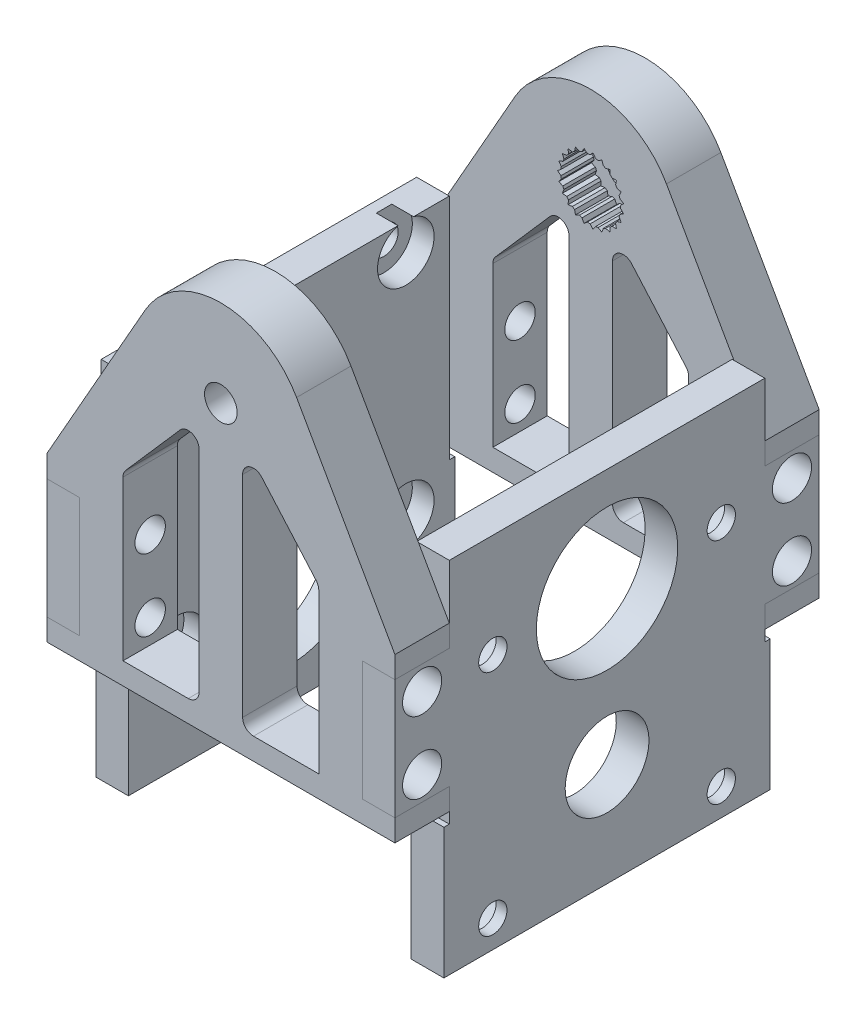
SolidWorks part; units mm, degrees
ref_plane "正面" through (0, 0, 0) normal (0, 0, 1) x (1, 0, 0)
ref_plane "平面" through (0, 0, 0) normal (0, 1, 0) x (1, 0, 0)
ref_plane "右側面" through (0, 0, 0) normal (1, 0, 0) x (0, 0, -1)
sketch "ｽｹｯﾁ1" plane through (0, 0, 0) normal (0, 0, 1) x (1, 0, 0)
  line L0 (-16, -12) -> (-16, -27)
  line L1 (-16, -27) -> (16, -27)
  line L2 (16, -27) -> (16, -12)
  line L3 (16, -12) -> (6.9593, 3.9457)
  line L4 (-6.9593, 3.9457) -> (-16, -12)
  line L5 (0, 0) -> (0, -27) construction
  line L6 (-16, -12) -> (16, -12) construction
  circle A0 centre (0, 0) radius 2.75
  arc A1 (6.9593, 3.9457) -> (-6.9593, 3.9457) centre (0, 0) ccw
  dimension "D1" = 5.5
  dimension "D6" = 8
  dimension "D2" = 16
  dimension "D3" = 16
  dimension "D4" = 12
  dimension "D5" = 15
extrude "ﾎﾞｽ - 押し出し1" add sketch "ｽｹｯﾁ1" along normal blind 3
sketch "ｽｹｯﾁ19" plane through (0, 0, 3) normal (0, 0, 1) x (1, 0, 0)
  line L0 (0, 0) -> (0, 2.75) construction
  line L1 (0, 0) -> (0.3745, 2.7244) construction
  line L2 (0, 0) -> (0.7419, 2.648) construction
  line L3 (0, 0) -> (1.0956, 2.5223) construction
  line L4 (0, 0) -> (1.4289, 2.3497) construction
  line L5 (0, 0) -> (1.7355, 2.1332) construction
  line L6 (0, 0) -> (2.0098, 1.877) construction
  line L7 (0, 0) -> (2.2467, 1.5859) construction
  line L8 (0, 0) -> (2.4417, 1.2652) construction
  line L9 (0, 0) -> (2.5912, 0.9209) construction
  line L10 (0, 0) -> (2.6925, 0.5595) construction
  line L11 (0, 0) -> (2.7436, 0.1877) construction
  line L12 (0, 0) -> (2.7436, -0.1877) construction
  line L13 (0, 0) -> (2.6925, -0.5595) construction
  line L14 (0, 0) -> (2.5912, -0.9209) construction
  line L15 (0, 0) -> (2.4417, -1.2652) construction
  line L16 (0, 0) -> (2.2467, -1.5859) construction
  line L17 (0, 0) -> (2.0098, -1.877) construction
  line L18 (0, 0) -> (1.7355, -2.1332) construction
  line L19 (0, 0) -> (1.4289, -2.3497) construction
  line L20 (0, 0) -> (1.0956, -2.5223) construction
  line L21 (0, 0) -> (0.7419, -2.648) construction
  line L22 (0, 0) -> (0.3745, -2.7244) construction
  line L23 (0, 0) -> (0, -2.75) construction
  line L24 (0, 0) -> (-0.3745, -2.7244) construction
  line L25 (0, 0) -> (-0.7419, -2.648) construction
  line L26 (0, 0) -> (-1.0956, -2.5223) construction
  line L27 (0, 0) -> (-1.4289, -2.3497) construction
  line L28 (0, 0) -> (-1.7355, -2.1332) construction
  line L29 (0, 0) -> (-2.0098, -1.877) construction
  line L30 (0, 0) -> (-2.2467, -1.5859) construction
  line L31 (0, 0) -> (-2.4417, -1.2652) construction
  line L32 (0, 0) -> (-2.5912, -0.9209) construction
  line L33 (0, 0) -> (-2.6925, -0.5595) construction
  line L34 (0, 0) -> (-2.7436, -0.1877) construction
  line L35 (0, 0) -> (-2.7436, 0.1877) construction
  line L36 (0, 0) -> (-2.6925, 0.5595) construction
  line L37 (0, 0) -> (-2.5912, 0.9209) construction
  line L38 (0, 0) -> (-2.4417, 1.2652) construction
  line L39 (0, 0) -> (-2.2467, 1.5859) construction
  line L40 (0, 0) -> (-2.0098, 1.877) construction
  line L41 (0, 0) -> (-1.7355, 2.1332) construction
  line L42 (0, 0) -> (-1.4289, 2.3497) construction
  line L43 (0, 0) -> (-1.0956, 2.5223) construction
  line L44 (0, 0) -> (-0.7419, 2.648) construction
  line L45 (0, 0) -> (-0.3745, 2.7244) construction
  line L46 (0, 0) -> (0.2081, 3.0429) construction
  line L47 (0.2081, 3.0429) -> (-0.0626, 2.7493)
  line L48 (0.2081, 3.0429) -> (0.4364, 2.7152)
  line L49 (-0.0626, 2.7493) -> (0, 0) construction
  line L50 (0, 0) -> (0.4364, 2.7152) construction
  line L51 (1.0214, 2.8739) -> (0.6815, 2.6642)
  line L52 (1.0214, 2.8739) -> (1.1527, 2.4967)
  line L53 (1.7589, 2.4918) -> (1.375, 2.3816)
  line L54 (1.7589, 2.4918) -> (1.7836, 2.0931)
  line L55 (2.3659, 1.9248) -> (1.9666, 1.9223)
  line L56 (2.3659, 1.9248) -> (2.2822, 1.5343)
  line L57 (2.7975, 1.2151) -> (2.4123, 1.3204)
  line L58 (2.7975, 1.2151) -> (2.6115, 0.8617)
  line L59 (3.0216, 0.4153) -> (2.679, 0.6206)
  line L60 (3.0216, 0.4153) -> (2.7472, 0.1252)
  line L61 (3.0216, -0.4153) -> (2.7472, -0.1252)
  line L62 (3.0216, -0.4153) -> (2.679, -0.6206)
  line L63 (2.7975, -1.2151) -> (2.6115, -0.8617)
  line L64 (2.7975, -1.2151) -> (2.4123, -1.3204)
  line L65 (2.3659, -1.9248) -> (2.2822, -1.5343)
  line L66 (2.3659, -1.9248) -> (1.9666, -1.9223)
  line L67 (1.7589, -2.4918) -> (1.7836, -2.0931)
  line L68 (1.7589, -2.4918) -> (1.375, -2.3816)
  line L69 (1.0214, -2.8739) -> (1.1527, -2.4967)
  line L70 (1.0214, -2.8739) -> (0.6815, -2.6642)
  line L71 (0.2081, -3.0429) -> (0.4364, -2.7152)
  line L72 (0.2081, -3.0429) -> (-0.0626, -2.7493)
  line L73 (-0.6205, -2.9862) -> (-0.3123, -2.7322)
  line L74 (-0.6205, -2.9862) -> (-0.802, -2.6304)
  line L75 (-1.4032, -2.708) -> (-1.0379, -2.5466)
  line L76 (-1.4032, -2.708) -> (-1.482, -2.3165)
  line L77 (-2.0818, -2.229) -> (-1.6865, -2.1722)
  line L78 (-2.0818, -2.229) -> (-2.052, -1.8308)
  line L79 (-2.606, -1.5847) -> (-2.21, -1.6366)
  line L80 (-2.606, -1.5847) -> (-2.4699, -1.2093)
  line L81 (-2.9369, -0.8229) -> (-2.5696, -0.9797)
  line L82 (-2.9369, -0.8229) -> (-2.7045, -0.4981)
  line L83 (-3.05, 0) -> (-2.7386, -0.2501)
  line L84 (-3.05, 0) -> (-2.7386, 0.2501)
  line L85 (-2.9369, 0.8229) -> (-2.7045, 0.4981)
  line L86 (-2.9369, 0.8229) -> (-2.5696, 0.9797)
  line L87 (-2.606, 1.5847) -> (-2.4699, 1.2093)
  line L88 (-2.606, 1.5847) -> (-2.21, 1.6366)
  line L89 (-2.0818, 2.229) -> (-2.052, 1.8308)
  line L90 (-2.0818, 2.229) -> (-1.6865, 2.1722)
  line L91 (-1.4032, 2.708) -> (-1.482, 2.3165)
  line L92 (-1.4032, 2.708) -> (-1.0379, 2.5466)
  line L93 (-0.6205, 2.9862) -> (-0.802, 2.6304)
  line L94 (-0.6205, 2.9862) -> (-0.3123, 2.7322)
  circle A0 centre (0, 0) radius 2.75 construction
  arc A1 (0, 2.75) -> (0.3745, 2.7244) centre (0, 0) cw construction
  circle A2 centre (0, 0) radius 3.05 construction
  arc A3 (-0.0626, 2.7493) -> (0.4364, 2.7152) centre (0, 0) cw
  arc A4 (0.6815, 2.6642) -> (1.1527, 2.4967) centre (0, 0) cw
  arc A5 (1.375, 2.3816) -> (1.7836, 2.0931) centre (0, 0) cw
  arc A6 (1.9666, 1.9223) -> (2.2822, 1.5343) centre (0, 0) cw
  arc A7 (2.4123, 1.3204) -> (2.6115, 0.8617) centre (0, 0) cw
  arc A8 (2.679, 0.6206) -> (2.7472, 0.1252) centre (0, 0) cw
  arc A9 (2.7472, -0.1252) -> (2.679, -0.6206) centre (0, 0) cw
  arc A10 (2.6115, -0.8617) -> (2.4123, -1.3204) centre (0, 0) cw
  arc A11 (2.2822, -1.5343) -> (1.9666, -1.9223) centre (0, 0) cw
  arc A12 (1.7836, -2.0931) -> (1.375, -2.3816) centre (0, 0) cw
  arc A13 (1.1527, -2.4967) -> (0.6815, -2.6642) centre (0, 0) cw
  arc A14 (0.4364, -2.7152) -> (-0.0626, -2.7493) centre (0, 0) cw
  arc A15 (-0.3123, -2.7322) -> (-0.802, -2.6304) centre (0, 0) cw
  arc A16 (-1.0379, -2.5466) -> (-1.482, -2.3165) centre (0, 0) cw
  arc A17 (-1.6865, -2.1722) -> (-2.052, -1.8308) centre (0, 0) cw
  arc A18 (-2.21, -1.6366) -> (-2.4699, -1.2093) centre (0, 0) cw
  arc A19 (-2.5696, -0.9797) -> (-2.7045, -0.4981) centre (0, 0) cw
  arc A20 (-2.7386, -0.2501) -> (-2.7386, 0.2501) centre (0, 0) cw
  arc A21 (-2.7045, 0.4981) -> (-2.5696, 0.9797) centre (0, 0) cw
  arc A22 (-2.4699, 1.2093) -> (-2.21, 1.6366) centre (0, 0) cw
  arc A23 (-2.052, 1.8308) -> (-1.6865, 2.1722) centre (0, 0) cw
  arc A24 (-1.482, 2.3165) -> (-1.0379, 2.5466) centre (0, 0) cw
  arc A25 (-0.802, 2.6304) -> (-0.3123, 2.7322) centre (0, 0) cw
  point P7 (0.1877, 2.7436)
  point P52 (0, 0)
  point P60 (0.1877, 2.7436)
  point P126 (0, 0)
  dimension "D2" = 6.1
  dimension "D3" = 10.435
  dimension "D1" = 46
  dimension "D4" = 23
extrude "ｶｯﾄ - 押し出し6" cut sketch "ｽｹｯﾁ19" against normal through all
sketch "ｽｹｯﾁ2" plane through (0, 0, 0) normal (0, 0, -1) x (-1, 0, 0)
  line L5 (16, -12) -> (6.9593, 3.9457)
  line L6 (-6.9593, 3.9457) -> (-16, -12)
  line L7 (-16, -12) -> (-16, -27)
  line L8 (-16, -27) -> (16, -27)
  line L9 (16, -27) -> (16, -12)
  line L10 (16, -12) -> (6.9593, 3.9457)
  line L11 (-6.9593, 3.9457) -> (-16, -12)
  line L12 (-16, -12) -> (-16, -27)
  line L13 (-16, -27) -> (16, -27)
  line L14 (16, -27) -> (16, -12)
  arc A1 (6.9593, 3.9457) -> (-6.9593, 3.9457) centre (0, 0) ccw
  arc A2 (6.9593, 3.9457) -> (-6.9593, 3.9457) centre (0, 0) ccw
  dimension "D1" = 0
extrude "ﾎﾞｽ - 押し出し2" add sketch "ｽｹｯﾁ2" along normal blind 2
ref_plane "平面1" through (0, 0, 33.5) normal (0, 0, 1) x (1, 0, 0)
sketch "ｽｹｯﾁ3" plane through (0, 0, 33.5) normal (0, 0, 1) x (1, 0, 0)
  line L5 (-6.9593, 3.9457) -> (-16, -12)
  line L6 (-16, -12) -> (-16, -27)
  line L7 (-16, -27) -> (16, -27)
  line L8 (16, -27) -> (16, -12)
  line L9 (16, -12) -> (6.9593, 3.9457)
  line L10 (-6.9593, 3.9457) -> (-16, -12)
  line L11 (-16, -12) -> (-16, -27)
  line L12 (-16, -27) -> (16, -27)
  line L13 (16, -27) -> (16, -12)
  line L14 (16, -12) -> (6.9593, 3.9457)
  circle A0 centre (0, 0) radius 2.75 construction
  arc A1 (6.9593, 3.9457) -> (-6.9593, 3.9457) centre (0, 0) ccw
  arc A2 (6.9593, 3.9457) -> (-6.9593, 3.9457) centre (0, 0) ccw
  circle A3 centre (0, 0) radius 2.75 construction
  circle A4 centre (0, 0) radius 3.6
  dimension "D2" = 7.2
  dimension "D1" = 0
extrude "ﾎﾞｽ - 押し出し3" add sketch "ｽｹｯﾁ3" against normal blind 1.5 separate body
sketch "ｽｹｯﾁ4" plane through (0, 0, 33.5) normal (0, 0, 1) x (1, 0, 0)
  line L5 (-6.9593, 3.9457) -> (-16, -12)
  line L6 (-16, -12) -> (-16, -27)
  line L7 (-16, -27) -> (16, -27)
  line L8 (16, -27) -> (16, -12)
  line L9 (16, -12) -> (6.9593, 3.9457)
  line L10 (-6.9593, 3.9457) -> (-16, -12)
  line L11 (-16, -12) -> (-16, -27)
  line L12 (-16, -27) -> (16, -27)
  line L13 (16, -27) -> (16, -12)
  line L14 (16, -12) -> (6.9593, 3.9457)
  arc A1 (6.9593, 3.9457) -> (-6.9593, 3.9457) centre (0, 0) ccw
  arc A2 (6.9593, 3.9457) -> (-6.9593, 3.9457) centre (0, 0) ccw
  dimension "D1" = 0
extrude "ﾎﾞｽ - 押し出し4" add sketch "ｽｹｯﾁ4" along normal blind 3.5
sketch "ｽｹｯﾁ5" plane through (0, 0, -2) normal (0, 0, -1) x (-1, 0, 0)
  line L0 (-16, -12) -> (-16, -27) construction
  line L1 (-16, -14) -> (-13, -14)
  line L2 (-16, -14) -> (-16, -25)
  line L3 (-16, -25) -> (-13, -25)
  line L4 (-13, -14) -> (-13, -25)
  line L5 (-16, -14) -> (-13, -25) construction
  line L6 (-16, -25) -> (-13, -14) construction
  line L7 (16, -27) -> (16, -12) construction
  line L8 (16, -14) -> (13, -14)
  line L9 (16, -14) -> (16, -25)
  line L10 (16, -25) -> (13, -25)
  line L11 (13, -14) -> (13, -25)
  line L12 (16, -14) -> (13, -25) construction
  line L13 (16, -25) -> (13, -14) construction
  line L14 (-16, -27) -> (16, -27) construction
  line L15 (-16, -12) -> (16, -12) construction
  line L16 (-6.9593, 3.9457) -> (-16, -12) construction
  point P4 (-14.5, -19.5)
  point P11 (14.5, -19.5)
  dimension "D1" = 3
  dimension "D2" = 3
  dimension "D3" = 2
  dimension "D4" = 2
extrude "ｶｯﾄ - 押し出し1" cut sketch "ｽｹｯﾁ5" against normal through all
sketch "ｽｹｯﾁ6" plane through (13, 0, 0) normal (1, 0, 0) x (0, 0, -1)
  line L0 (2, -14) -> (-3, -14)
  line L1 (-3, -14) -> (-3, -7)
  line L2 (-3, -7) -> (-32, -7)
  line L3 (-32, -12) -> (-32, 3.9457) construction
  line L4 (-32, -7) -> (-32, -14)
  line L5 (-32, -14) -> (-37, -14)
  line L6 (-37, -14) -> (-37, -25)
  line L7 (-37, -25) -> (-32, -25)
  line L8 (-32, -25) -> (-32, -40)
  line L9 (-32, -40) -> (-3, -40)
  line L10 (-3, -40) -> (-3, -25)
  line L11 (-3, -25) -> (2, -25)
  line L12 (2, -25) -> (2, -14)
  line L13 (-17.5, -7) -> (-17.5, -40) construction
  line L14 (0, 0) -> (-33.5, 0) construction
  line L15 (-7, -37.5) -> (-28, -37.5) construction
  line L16 (-7, -37.5) -> (-7, -16.5) construction
  line L17 (-7, -16.5) -> (-28, -16.5) construction
  line L18 (-28, -37.5) -> (-28, -16.5) construction
  line L19 (-7, -37.5) -> (-28, -16.5) construction
  line L20 (-7, -16.5) -> (-28, -37.5) construction
  line L21 (-33.5, 3.3394) -> (-33.5, -3.3394) construction
  line L22 (2, -23.5) -> (-37, -23.5) construction
  circle A0 centre (-17.5, -16.5) radius 6.5
  circle A1 centre (-28, -16.5) radius 1.3
  circle A2 centre (-7, -16.5) radius 1.3
  circle A3 centre (-28, -37.5) radius 1.3
  circle A4 centre (-7, -37.5) radius 1.3
  circle A5 centre (-17.5, -30.5) radius 6.5 construction
  circle A6 centre (-17.5, -30.5) radius 3.85
  point P24 (-17.5, -27)
  point P43 (-17.5, -23.5)
  dimension "D6" = 2.6
  dimension "D8" = 13
  dimension "D10" = 7.7
  dimension "D1" = 21
  dimension "D2" = 21
  dimension "D3" = 14.5
  dimension "D4" = 13
  dimension "D5" = 21
  dimension "D7" = 20
  dimension "D9" = 27
extrude "ﾎﾞｽ - 押し出し5" add sketch "ｽｹｯﾁ6" along normal up to surface (3 mm away) separate body up to face at (16, -13, 0.5)
sketch "ｽｹｯﾁ8" plane through (-13, 0, 0) normal (-1, 0, 0) x (0, 0, 1)
  line L0 (3, -7) -> (3, -40) construction
  line L1 (32, -7) -> (32, -40) construction
  line L2 (3, -23.5) -> (32, -23.5) construction
  line L12 (-2, -14) -> (-2, -25)
  line L13 (-2, -25) -> (3, -25)
  line L14 (3, -25) -> (3, -40)
  line L15 (3, -40) -> (32, -40)
  line L16 (32, -40) -> (32, -25)
  line L17 (32, -25) -> (37, -25)
  line L18 (37, -25) -> (37, -14)
  line L19 (37, -14) -> (32, -14)
  line L20 (32, -14) -> (32, -7)
  line L21 (32, -7) -> (3, -7)
  line L22 (3, -7) -> (3, -14)
  line L23 (3, -14) -> (-2, -14)
  line L24 (-2, -14) -> (-2, -25)
  line L25 (-2, -25) -> (3, -25)
  line L26 (3, -25) -> (3, -40)
  line L27 (3, -40) -> (32, -40)
  line L28 (32, -40) -> (32, -25)
  line L29 (32, -25) -> (37, -25)
  line L30 (37, -25) -> (37, -14)
  line L31 (37, -14) -> (32, -14)
  line L32 (32, -14) -> (32, -7)
  line L33 (32, -7) -> (3, -7)
  line L34 (3, -7) -> (3, -14)
  line L35 (3, -14) -> (-2, -14)
  circle A0 centre (28, -37.5) radius 1.3 construction
  circle A1 centre (28, -16.5) radius 1.3 construction
  circle A2 centre (7, -37.5) radius 1.3 construction
  circle A3 centre (17.5, -16.5) radius 6.5 construction
  circle A4 centre (7, -16.5) radius 1.3 construction
  circle A5 centre (28, -37.5) radius 1.3 construction
  circle A6 centre (28, -16.5) radius 1.3 construction
  circle A7 centre (7, -37.5) radius 1.3 construction
  circle A8 centre (17.5, -16.5) radius 6.5 construction
  circle A9 centre (7, -16.5) radius 1.3 construction
  circle A10 centre (28, -9.5) radius 1.3
  circle A11 centre (7, -9.5) radius 1.3
  circle A12 centre (28, -30.5) radius 1.3
  circle A13 centre (17.5, -30.5) radius 6.5
  circle A14 centre (7, -30.5) radius 1.3
  circle A15 centre (17.5, -16.5) radius 3.85
  dimension "D2" = 7.7
  dimension "D1" = 0
extrude "ﾎﾞｽ - 押し出し6" add sketch "ｽｹｯﾁ8" along normal up to surface (3 mm away) separate body up to face at (-16, -26, 0.5)
sketch "ｽｹｯﾁ7" plane through (0, 0, -2) normal (0, 0, -1) x (-1, 0, 0)
  line L0 (0, 0) -> (0, -13.5) construction
  line L1 (-16, -27) -> (16, -27) construction
  line L2 (9, -25) -> (-9, -25) construction
  line L3 (9, -25) -> (9, -2) construction
  line L4 (9, -2) -> (-9, -2) construction
  line L5 (-9, -25) -> (-9, -2) construction
  line L6 (9, -25) -> (-9, -2) construction
  line L7 (9, -2) -> (-9, -25) construction
  line L8 (-13, -25) -> (-13, -14) construction
  line L9 (-9, -25) -> (-3, -25)
  line L10 (-2, -24) -> (-2, -4.6614)
  line L11 (-3.7526, -4.0029) -> (-8.7526, -9.7172)
  line L12 (-9, -10.3757) -> (-9, -25)
  line L15 (-16, -14) -> (-13, -14) construction
  line L16 (9, -25) -> (3, -25)
  line L17 (9, -10.3757) -> (9, -25)
  line L18 (3.7526, -4.0029) -> (8.7526, -9.7172)
  line L19 (2, -24) -> (2, -4.6614)
  circle A0 centre (0, 0) radius 1.5
  arc A2 (3, -25) -> (2, -24) centre (3, -24) cw
  arc A3 (-3, -25) -> (-2, -24) centre (-3, -24) ccw
  arc A5 (-2, -4.6614) -> (-3.7526, -4.0029) centre (-3, -4.6614) ccw
  arc A6 (3.7526, -4.0029) -> (2, -4.6614) centre (3, -4.6614) ccw
  arc A7 (9, -10.3757) -> (8.7526, -9.7172) centre (8, -10.3757) ccw
  arc A8 (-8.7526, -9.7172) -> (-9, -10.3757) centre (-8, -10.3757) ccw
  point P28 (2, -25)
  point P31 (-2, -25)
  point P37 (-2, -2)
  point P40 (2, -2)
  point P43 (9, -10)
  point P46 (-9, -10)
  dimension "D1" = 3
  dimension "D8" = 1
  dimension "D2" = 2
  dimension "D3" = 4
  dimension "D4" = 23
  dimension "D5" = 4
  dimension "D6" = 7
extrude "ｶｯﾄ - 押し出し2" cut sketch "ｽｹｯﾁ7" against normal through all
sketch "ｽｹｯﾁ10" plane through (16, 0, 0) normal (1, 0, 0) x (0, 0, -1)
  line L4 (-34.5, -12) -> (-34.5, -27) construction
  line L5 (-32, -12) -> (-37, -12) construction
  line L6 (-32, -27) -> (-37, -27) construction
  line L8 (-0.5, -12) -> (-0.5, -27) construction
  line L9 (-3, -12) -> (2, -12) construction
  line L10 (-3, -27) -> (2, -27) construction
  line L11 (-37, -14) -> (-32, -14) construction
  line L14 (-32, -25) -> (-37, -25) construction
  line L15 (-3, -14) -> (2, -14) construction
  line L16 (2, -25) -> (-3, -25) construction
  point P26 (-34.5, -16.2)
  point P28 (-34.5, -22.8)
  point P30 (-0.5, -16.2)
  point P32 (-0.5, -22.8)
  dimension "D1" = 2.2
  dimension "D2" = 2.2
  dimension "D3" = 2.2
  dimension "D4" = 2.2
hole_wizard "Ø2.8 (2.8) 直径の穴1" positions "ｽｹｯﾁ10" profile "ｽｹｯﾁ11" hole size "Ø2.8" standard "JIS"
sketch "ｽｹｯﾁ11" plane through (16, -22.8, 0.5) normal (0, 1, 0) x (0, 0, -1)
  line L0 (0, 0) -> (0, 14)
  line L1 (0, 14) -> (1.4, 13.1588)
  line L2 (1.4, 13.1588) -> (1.4, 0)
  line L5 (1.4, 0) -> (0, 0)
  line L10 (0, 14) -> (-1.4, 13.1588) construction
  line L11 (0, -6.35) -> (0, 107.95) construction
  dimension "穴の直径" = 2.8
  dimension "穴の深さ" = 14
  dimension "ﾄﾞﾘﾙ角度" = 118
hole_wizard "Ø2.8 (2.8) 直径の穴2" positions "ｽｹｯﾁ12" profile "ｽｹｯﾁ13" hole size "Ø2.8" standard "JIS"
sketch "ｽｹｯﾁ12" plane through (-16, 0, 0) normal (-1, 0, 0) x (0, 0, 1)
  point P0 (34.5, -16.2)
  point P3 (34.5, -22.8)
  point P6 (0.5, -16.2)
  point P9 (0.5, -22.8)
sketch "ｽｹｯﾁ13" plane through (-16, -16.2, 34.5) normal (0, 1, 0) x (0, 0, 1)
  line L0 (0, 0) -> (0, 14)
  line L1 (0, 14) -> (1.4, 13.1588)
  line L2 (1.4, 13.1588) -> (1.4, 0)
  line L5 (1.4, 0) -> (0, 0)
  line L10 (0, 14) -> (-1.4, 13.1588) construction
  line L11 (0, -6.35) -> (0, 107.95) construction
  dimension "穴の直径" = 2.8
  dimension "穴の深さ" = 14
  dimension "ﾄﾞﾘﾙ角度" = 118
hole_wizard "Ø3.6 (3.6) 直径の穴1" positions "ｽｹｯﾁ14" profile "ｽｹｯﾁ16" hole size "Ø3.6" standard "JIS" end condition through all
sketch "ｽｹｯﾁ14" plane through (16, 0, 0) normal (1, 0, 0) x (0, 0, -1)
  point P0 (-34.5, -16.2)
  point P3 (-34.5, -22.8)
  point P6 (-0.5, -16.2)
  point P9 (-0.5, -22.8)
sketch "ｽｹｯﾁ16" plane through (16, -16.2, 34.5) normal (0, 1, 0) x (0, 0, -1)
  line L0 (0, 0) -> (0, 32)
  line L1 (0, 32) -> (1.8, 32)
  line L2 (1.8, 32) -> (1.8, 0)
  line L5 (1.8, 0) -> (0, 0)
  line L11 (0, -6.35) -> (0, 107.95) construction
  dimension "通し穴の直径" = 3.6
  dimension "通し穴の深さ" = 32
sketch "ｽｹｯﾁ17" plane through (13, 0, 0) normal (-1, 0, 0) x (0, 0, 1)
  circle A0 centre (28, -37.5) radius 1.3 construction
  circle A1 centre (7, -37.5) radius 1.3 construction
  circle A2 centre (28, -16.5) radius 1.3 construction
  circle A3 centre (7, -16.5) radius 1.3 construction
  circle A4 centre (28, -37.5) radius 1.3 construction
  circle A5 centre (7, -37.5) radius 1.3 construction
  circle A6 centre (28, -16.5) radius 1.3 construction
  circle A7 centre (7, -16.5) radius 1.3 construction
  circle A8 centre (7, -16.5) radius 2.6
  circle A9 centre (7, -37.5) radius 2.6
  circle A10 centre (28, -37.5) radius 2.6
  circle A11 centre (28, -16.5) radius 2.6
  dimension "D1" = 5.2
extrude "ｶｯﾄ - 押し出し4" cut sketch "ｽｹｯﾁ17" against normal blind 2
sketch "ｽｹｯﾁ18" plane through (-13, 0, 0) normal (1, 0, 0) x (0, 0, -1)
  circle A0 centre (-28, -30.5) radius 1.3 construction
  circle A1 centre (-28, -9.5) radius 1.3 construction
  circle A2 centre (-7, -9.5) radius 1.3 construction
  circle A3 centre (-28, -30.5) radius 1.3 construction
  circle A4 centre (-28, -9.5) radius 1.3 construction
  circle A5 centre (-7, -9.5) radius 1.3 construction
  circle A6 centre (-7, -30.5) radius 1.3 construction
  circle A7 centre (-7, -30.5) radius 1.3 construction
  circle A8 centre (-28, -9.5) radius 2.6
  circle A9 centre (-28, -30.5) radius 2.6
  circle A10 centre (-7, -30.5) radius 2.6
  circle A11 centre (-7, -9.5) radius 2.6
  dimension "D1" = 5.2
extrude "ｶｯﾄ - 押し出し5" cut sketch "ｽｹｯﾁ18" against normal blind 2
sketch "ｽｹｯﾁ20" plane through (0, 0, 32) normal (0, 0, 1) x (1, 0, 0)
  line L0 (-13, -40) -> (-13, -25) construction
  line L1 (-16, -40) -> (-13, -40)
  line L2 (-16, -40) -> (-16, -28)
  line L3 (-16, -28) -> (-13, -28)
  line L4 (-13, -40) -> (-13, -28)
  line L5 (16, -40) -> (16, -25) construction
  line L6 (13, -40) -> (16, -40)
  line L7 (13, -40) -> (13, -28)
  line L8 (13, -28) -> (16, -28)
  line L9 (16, -40) -> (16, -28)
  line L10 (-16, -27) -> (16, -27) construction
  dimension "D1" = 1
extrude "ﾎﾞｽ - 押し出し7" add sketch "ｽｹｯﾁ20" along normal blind 0.5
sketch "ｽｹｯﾁ21" plane through (0, 0, 3) normal (0, 0, -1) x (-1, 0, 0)
  line L4 (-16, -40) -> (-13, -40)
  line L5 (-16, -28) -> (-16, -40)
  line L6 (-13, -28) -> (-16, -28)
  line L7 (-13, -40) -> (-13, -28)
  line L8 (-16, -40) -> (-13, -40)
  line L9 (-16, -28) -> (-16, -40)
  line L10 (-13, -28) -> (-16, -28)
  line L11 (-13, -40) -> (-13, -28)
  line L12 (13, -40) -> (16, -40)
  line L13 (13, -28) -> (13, -40)
  line L14 (16, -28) -> (13, -28)
  line L15 (16, -40) -> (16, -28)
  line L16 (13, -40) -> (16, -40)
  line L17 (13, -28) -> (13, -40)
  line L18 (16, -28) -> (13, -28)
  line L19 (16, -40) -> (16, -28)
  dimension "D1" = 0
  dimension "D2" = 0
extrude "ﾎﾞｽ - 押し出し8" add sketch "ｽｹｯﾁ21" along normal blind 0.5
equation "\"D2@ｽｹｯﾁ5\"=\"D1@ｽｹｯﾁ5\""
equation "\"D8@ｽｹｯﾁ6\"=12.5+0.5"
equation "\"D1@ｽｹｯﾁ10\"=\"D2@ｽｹｯﾁ10\""
equation "\"D3@ｽｹｯﾁ10\"=\"D2@ｽｹｯﾁ10\""
equation "\"D4@ｽｹｯﾁ10\"=\"D2@ｽｹｯﾁ10\""
equation "\"D3@ｽｹｯﾁ19\"=360/23*2/3"
